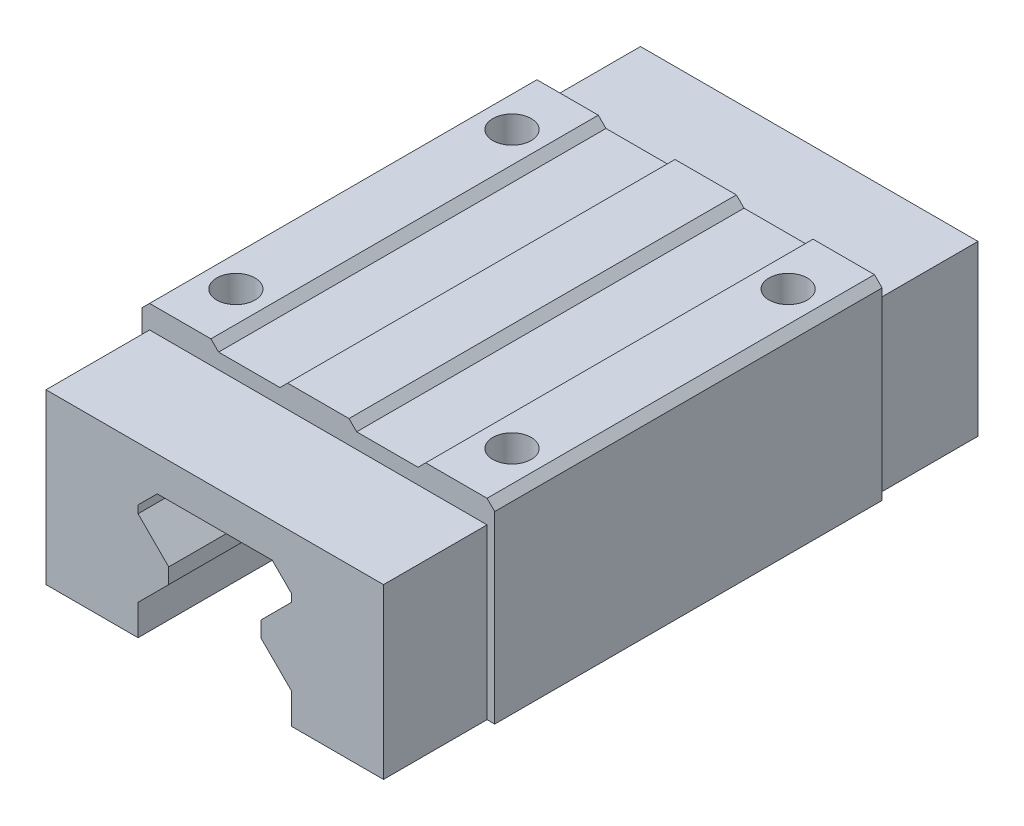
SolidWorks part; units mm, degrees
material "1.0402 (C22)"
ref_plane "Płaszczyzna przednia" through (0, 0, 0) normal (0, 0, 1) x (1, 0, 0)
ref_plane "Płaszczyzna górna" through (0, 0, 0) normal (0, 1, 0) x (1, 0, 0)
ref_plane "Płaszczyzna prawa" through (0, 0, 0) normal (1, 0, 0) x (0, 0, -1)
sketch "Szkic1" plane through (0, 0, 0) normal (0, 0, 1) x (1, 0, 0)
  line L0 (0, 31.3136) -> (0, -16.2227) construction
  line L2 (-10, 0) -> (-10, 4)
  line L3 (-10, 4) -> (-6, 8)
  line L4 (-6, 8) -> (-6, 10)
  line L5 (-6, 10) -> (-10, 14)
  line L6 (-10, 14) -> (-10, 15)
  line L7 (-10, 15) -> (-7.5, 17.5)
  line L8 (-7.5, 17.5) -> (7.5, 17.5)
  line L9 (10, 15) -> (7.5, 17.5)
  line L10 (10, 14) -> (10, 15)
  line L11 (6, 10) -> (10, 14)
  line L12 (6, 8) -> (6, 10)
  line L13 (10, 4) -> (6, 8)
  line L14 (10, 0) -> (10, 4)
  line L15 (-10, 0) -> (-22, 0)
  line L16 (-22, 0) -> (-22, 22)
  line L17 (-22, 22) -> (22, 22)
  line L18 (22, 22) -> (22, 0)
  line L19 (22, 0) -> (10, 0)
  point P5 (-6, 9)
  point P14 (0, 0)
  point P16 (0, 17.5)
  point P22 (0, 0)
  dimension "D1" = 20
  dimension "D2" = 12
  dimension "D3" = 1
  dimension "D4" = 2
  dimension "D5" = 17.5
  dimension "D6" = 8.5
  dimension "D7" = 135
  dimension "D8" = 22
  dimension "D9" = 44
  dimension "D10" = 44
extrude "Dodanie-wyciągnięcie1" add sketch "Szkic1" along normal blind 77.5
sketch "Szkic2" plane through (0, 22, 0) normal (0, 1, 0) x (1, 0, 0)
  line L0 (22, -77.5) -> (22, 0) construction
  line L1 (-23, -64) -> (23, -64)
  line L2 (-23, -64) -> (-23, -13.5)
  line L3 (-23, -13.5) -> (23, -13.5)
  line L4 (23, -64) -> (23, -13.5)
  line L5 (-23, -64) -> (23, -13.5) construction
  line L6 (-23, -13.5) -> (23, -64) construction
  point P0 (0, -38.75)
  point P7 (22, -38.75)
  point P8 (0, 0)
  dimension "D1" = 1
  dimension "D2" = 50.5
extrude "Dodanie-wyciągnięcie2" add sketch "Szkic2" along normal blind 3
sketch "Szkic3" plane through (0, 22, 0) normal (0, -1, 0) x (1, 0, 0)
  line L4 (-22, 13.5) -> (-22, 64)
  line L5 (-22, 64) -> (-23, 64)
  line L6 (-23, 64) -> (-23, 13.5)
  line L7 (-23, 13.5) -> (-22, 13.5)
  line L8 (-22, 13.5) -> (-22, 64)
  line L9 (-22, 64) -> (-23, 64)
  line L10 (-23, 64) -> (-23, 13.5)
  line L11 (-23, 13.5) -> (-22, 13.5)
  line L12 (23, 64) -> (22, 64)
  line L13 (22, 64) -> (22, 13.5)
  line L14 (22, 13.5) -> (23, 13.5)
  line L15 (23, 13.5) -> (23, 64)
  line L16 (23, 64) -> (22, 64)
  line L17 (22, 64) -> (22, 13.5)
  line L18 (22, 13.5) -> (23, 13.5)
  line L19 (23, 13.5) -> (23, 64)
  dimension "D1" = 0
  dimension "D2" = 0
extrude "Dodanie-wyciągnięcie3" add sketch "Szkic3" along normal blind 22
sketch "Szkic4" plane through (0, 25, 0) normal (0, 1, 0) x (1, 0, 0)
  line L0 (23, -13.5) -> (-23, -13.5) construction
  line L1 (-13, -13.5) -> (-5, -13.5)
  line L2 (-13, -13.5) -> (-13, -64)
  line L3 (-13, -64) -> (-5, -64)
  line L4 (-5, -13.5) -> (-5, -64)
  line L5 (-23, -64) -> (23, -64) construction
  line L6 (0, 25.66) -> (0, -112.5727) construction
  line L7 (13, -64) -> (5, -64)
  line L8 (5, -13.5) -> (5, -64)
  line L9 (13, -13.5) -> (5, -13.5)
  line L10 (13, -13.5) -> (13, -64)
  dimension "D1" = 8
  dimension "D2" = 10
extrude "Wytnij-wyciągnięcie1" cut sketch "Szkic4" against normal blind 1
chamfer "Sfazowanie1" distance 1 angle 45 6 edges at (-23, 25, 38.75) (-13, 25, 38.75) (-5, 25, 38.75) (5, 25, 38.75) (13, 25, 38.75) (23, 25, 38.75)
sketch "Szkic5" plane through (0, 25, 0) normal (0, 1, 0) x (1, 0, 0)
  line L0 (0, 12.0644) -> (0, -90.187) construction
  line L2 (22, -13.5) -> (14, -13.5) construction
  line L3 (22, -38.75) -> (-50.2899, -38.75) construction
  line L4 (22, -64) -> (22, -13.5) construction
  circle A0 centre (18, -20.75) radius 2.5
  circle A2 centre (18, -56.75) radius 2.5
  circle A3 centre (-18, -56.75) radius 2.5
  circle A4 centre (-18, -20.75) radius 2.5
  point P11 (18, -13.5)
  dimension "D1" = 5
  dimension "D2" = 36
hole_wizard "Otwory ustalające Ø5.0mm1" positions "Szkic6" profile "Szkic7" hole size "Ø5.0" standard "ISO"
sketch "Szkic6" plane through (0, 25, 0) normal (0, 1, 0) x (1, 0, 0)
  point P0 (-18, -20.75)
  point P3 (18, -20.75)
  point P6 (18, -56.75)
  point P9 (-18, -56.75)
sketch "Szkic7" plane through (-18, 25, 20.75) normal (1, 0, 0) x (0, 0, 1)
  line L0 (0, 0) -> (0, 11.5022)
  line L1 (0, 11.5022) -> (2.5, 10)
  line L2 (2.5, 10) -> (2.5, 0)
  line L5 (2.5, 0) -> (0, 0)
  line L10 (0, 11.5022) -> (-2.5, 10) construction
  line L11 (0, -6.35) -> (0, 107.95) construction
  dimension "Średnica otworu" = 5
  dimension "Głębokość otworu" = 10
  dimension "Kąt wiertła" = 118
